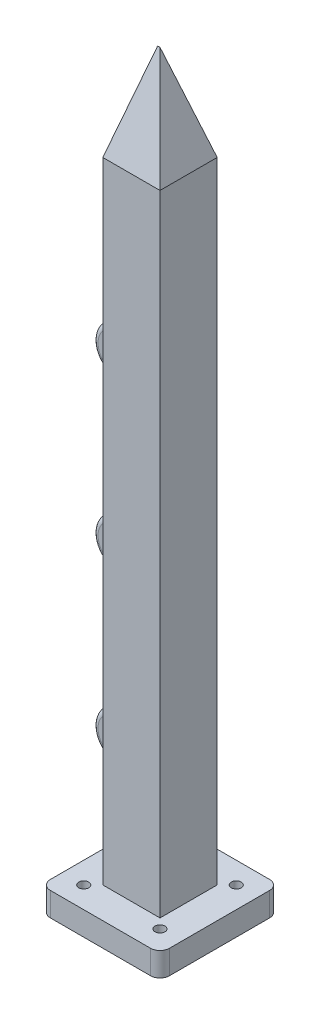
SolidWorks part; units mm, degrees
material "ABS PC"
ref_plane "Front Plane" through (0, 0, 0) normal (0, 0, 1) x (1, 0, 0)
ref_plane "Top Plane" through (0, 0, 0) normal (0, 1, 0) x (1, 0, 0)
ref_plane "Right Plane" through (0, 0, 0) normal (1, 0, 0) x (0, 0, -1)
sketch "Sketch1" plane through (0, 0, 0) normal (0, 1, 0) x (1, 0, 0)
  line L1 (0, 0) -> (25, 0)
  line L2 (0, 0) -> (0, 25)
  line L3 (0, 25) -> (25, 25)
  line L4 (25, 0) -> (25, 25)
  dimension "D1" = 25
  dimension "D2" = 25
extrude "Boss-Extrude1" add sketch "Sketch1" along normal blind 5
sketch "Sketch2" plane through (0, 5, 0) normal (0, 1, 0) x (1, 0, 0)
  line L0 (0, 0) -> (25, 0) construction
  line L1 (0, 25) -> (0, 0) construction
  line L2 (25, 0) -> (25, 25) construction
  line L3 (25, 25) -> (0, 25) construction
  circle A0 centre (4.5, 4.5) radius 1.05
  circle A1 centre (20.5, 4.5) radius 1.05
  circle A2 centre (20.5, 20.5) radius 1.05
  circle A3 centre (4.5, 20.5) radius 1.05
  dimension "D1" = 2.1
  dimension "D4" = 2.1
  dimension "D6" = 2.1
  dimension "D8" = 2.1
  dimension "D2" = 4.5
  dimension "D3" = 4.5
  dimension "D5" = 4.5
  dimension "D7" = 4.5
extrude "Cut-Extrude1" cut sketch "Sketch2" against normal blind 5
fillet "Fillet1" radius 2 4 edges at (0, 2.5, -25) (0, 2.5, 0) (25, 2.5, -25) (25, 2.5, 0)
sketch "Sketch3" plane through (0, 5, 0) normal (0, 1, 0) x (1, 0, 0)
  line L0 (2, 0) -> (23, 0) construction
  line L1 (6.5, 6.5) -> (18.5, 6.5)
  line L2 (6.5, 6.5) -> (6.5, 18.5)
  line L3 (6.5, 18.5) -> (18.5, 18.5)
  line L4 (18.5, 6.5) -> (18.5, 18.5)
  line L5 (25, 2) -> (25, 23) construction
  dimension "D1" = 12
  dimension "D2" = 6.5
  dimension "D3" = 6.5
extrude "Boss-Extrude2" add sketch "Sketch3" along normal blind 152.2
sketch "Sketch4" plane through (0, 157.2, 0) normal (0, 1, 0) x (1, 0, 0)
  line L1 (10, 15) -> (15, 15)
  line L2 (10, 15) -> (10, 10)
  line L3 (10, 10) -> (15, 10)
  line L4 (15, 15) -> (15, 10)
  line L5 (10, 15) -> (15, 10) construction
  line L6 (10, 10) -> (15, 15) construction
  point P0 (12.5, 12.5)
  dimension "D1" = 5
extrude "Cut-Extrude2" cut sketch "Sketch4" against normal blind 140
sketch "Sketch5" plane through (0, 157.2, 0) normal (0, 1, 0) x (1, 0, 0)
  line L1 (15, 15) -> (10, 15)
  line L2 (15, 15) -> (15, 10)
  line L3 (15, 10) -> (10, 10)
  line L4 (10, 15) -> (10, 10)
extrude "Boss-Extrude3" add sketch "Sketch5" against normal blind 20
sketch "Sketch7" plane through (18.5, 0, 0) normal (1, 0, 0) x (0, 0, -1)
  line L0 (12.5, 157.2) -> (18.5, 157.2)
  line L1 (6.5, 157.2) -> (18.5, 157.2) construction
  line L2 (18.5, 157.2) -> (18.5, 5) construction
  line L3 (18.5, 157.2) -> (18.5, 137.2)
  line L4 (18.5, 137.2) -> (12.5, 157.2)
  line L5 (6.5, 157.2) -> (6.5, 137.2)
  line L6 (6.5, 157.2) -> (6.5, 5) construction
  line L7 (6.5, 137.2) -> (12.5, 157.2)
  dimension "D1" = 20
  dimension "D2" = 20
sketch "Sketch10" plane through (6.5, 0, 0) normal (-1, 0, 0) x (0, 0, 1)
  line L0 (-6.5, 157.2) -> (-12.5, 157.2)
  line L1 (-6.5, 157.2) -> (-6.5, 5) construction
  line L2 (-18.5, 157.2) -> (-6.5, 157.2) construction
  line L3 (-12.5, 157.2) -> (-6.5, 157.2)
  line L4 (-6.5, 157.2) -> (-6.5, 137.2)
  line L5 (-6.5, 137.2) -> (-12.5, 157.2)
  line L6 (-12.5, 157.2) -> (-18.5, 157.2)
  line L7 (-18.5, 157.2) -> (-18.5, 137.2)
  line L8 (-18.5, 157.2) -> (-18.5, 5) construction
  line L9 (-18.5, 137.2) -> (-12.5, 157.2)
  line M2 (-6.5, 5) -> (-6.5, 157.2)
  line M3 (-6.5, 157.2) -> (-18.5, 157.2)
  line M4 (-18.5, 157.2) -> (-18.5, 5)
  dimension "D1" = 20
  dimension "D2" = 20
extrude "Cut-Extrude6" cut sketch "Sketch10" against normal blind 20 contours L5 M2 M3 | L9 M4 M3 region at (6.5, 150.5333, -8.5) region at (6.5, 150.5333, -16.5)
sketch "Sketch11" plane through (0, 0, -6.5) normal (0, 0, 1) x (1, 0, 0)
  line L0 (18.5, 137.2) -> (18.5, 157.2)
  line L1 (18.5, 157.2) -> (12.5, 157.2)
  line L2 (12.5, 157.2) -> (18.5, 137.2)
  line L3 (12.5, 157.2) -> (6.5, 157.2)
  line L4 (6.5, 157.2) -> (6.5, 185)
  line L5 (6.5, 185) -> (12.5, 157.2)
  dimension "D1" = 20
  dimension "D2" = 6
  dimension "D3" = 6
extrude "Cut-Extrude7" cut sketch "Sketch11" against normal blind 20 contours L4 L5 L3 | L1 L2 L0 region at (16.5, 150.5333, -6.5)
sketch "Sketch12" plane through (0, 0, -18.5) normal (0, 0, -1) x (-1, 0, 0)
  line L0 (-6.5, 137.2) -> (-6.5, 5) construction
  line L1 (-18.5, 5) -> (-6.5, 5) construction
  circle A0 centre (-6.5, 30) radius 5
  circle A1 centre (-4.5, 30) radius 1
  circle A2 centre (-6.5, 65) radius 5
  circle A3 centre (-4.5, 65) radius 1
  circle A4 centre (-6.5, 100) radius 5
  circle A5 centre (-4.5, 100) radius 1
  dimension "D1" = 10
  dimension "D2" = 2
  dimension "D5" = 10
  dimension "D6" = 2
  dimension "D11" = 10
  dimension "D12" = 2
  dimension "D13" = 2
  dimension "D3" = 25
  dimension "D4" = 25
  dimension "D7" = 2
  dimension "D8" = 2
  dimension "D9" = 60
  dimension "D10" = 60
  dimension "D14" = 95
  dimension "D15" = 95
extrude "Boss-Extrude4" add sketch "Sketch12" along normal blind 3 and the other way blind 3 from offset 6 offset against normal yes
fillet "Fillet2" radius 1 19 edges at (6.5, 30, -15.5) (6.5, 30, -9.5) (6.5, 65, -15.5) (6.5, 100, -9.5) (1.5, 30, -15.5) (6.5, 35, -12.5) (1.5, 30, -9.5) (6.5, 25, -12.5) (1.5, 65, -15.5) (6.5, 70, -12.5) (1.5, 65, -9.5) (6.5, 60, -12.5) (6.5, 65, -9.5) (1.5, 100, -9.5) (11.5, 100, -10) (1.5, 100, -15.5) (6.5, 105, -12.5) (6.5, 95, -12.5) (6.5, 100, -15.5)
sketch "Sketch13" plane through (0, 0, -18.5) normal (0, 0, -1) x (-1, 0, 0)
  line L0 (-6.5, 137.2) -> (-6.5, 157.2)
  line L1 (-6.5, 157.2) -> (-12, 157.2)
  line L2 (-12, 157.2) -> (-6.5, 137.2)
  dimension "D1" = 20
  dimension "D2" = 5.5
extrude "Cut-Extrude8" cut sketch "Sketch13" against normal blind 15
